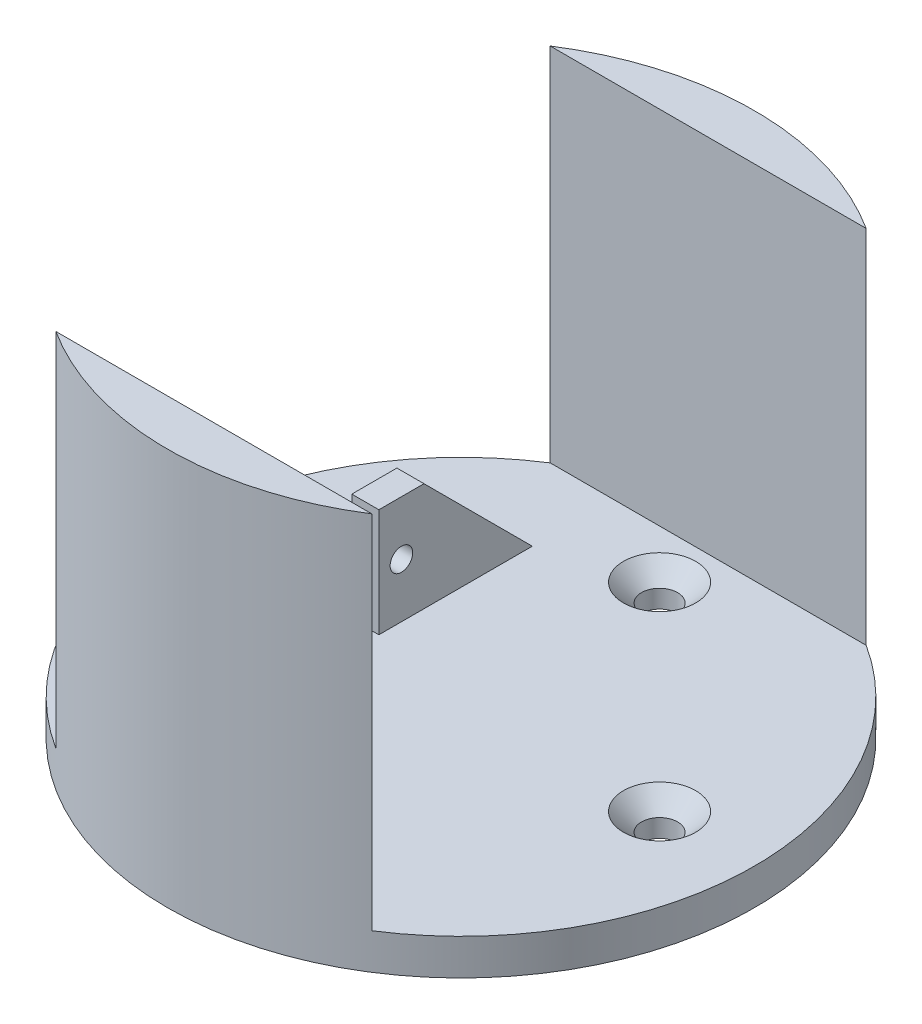
SolidWorks part; units mm, degrees
ref_plane "Front Plane" through (0, 0, 0) normal (0, 0, 1) x (1, 0, 0)
ref_plane "Top Plane" through (0, 0, 0) normal (0, 1, 0) x (1, 0, 0)
ref_plane "Right Plane" through (0, 0, 0) normal (1, 0, 0) x (0, 0, -1)
sketch "Sketch1" plane through (0, 0, 0) normal (0, 1, 0) x (1, 0, 0)
  circle A0 centre (0, 0) radius 32.5
  circle A1 centre (-22, 0) radius 2
  circle A2 centre (0, 22) radius 2
  circle A3 centre (22, 0) radius 2
  circle A4 centre (0, -22) radius 2
  point P14 (0, 0)
  dimension "D1" = 65
  dimension "D2" = 4
  dimension "D3" = 22
  dimension "D4" = 4
extrude "Boss-Extrude1" add sketch "Sketch1" along normal blind 4
sketch "Sketch2" plane through (0, 4, 0) normal (0, 1, 0) x (1, 0, 0)
  line L0 (17.5, 27.3861) -> (-17.5, 27.3861)
  line L1 (0, 0) -> (-10.9128, 0) construction
  line L2 (17.5, -27.3861) -> (-17.5, -27.3861)
  arc A0 (17.5, 27.3861) -> (-17.5, 27.3861) centre (0, 0) ccw
  arc A1 (17.5, -27.3861) -> (-17.5, -27.3861) centre (0, 0) cw
  circle A4 centre (0, 0) radius 32.5 construction
  dimension "D1" = 35
extrude "Boss-Extrude2" add sketch "Sketch2" along normal blind 40
chamfer "Chamfer1" distance 2 angle 45 4 edges at (0, 4, 24) (0, 4, -20) (22, 4, 2) (-22, 4, 2)
sketch "Sketch3" plane through (0, 4, 0) normal (0, 1, 0) x (1, 0, 0)
  line L0 (0, 0) -> (-7.2128, 0) construction
  line L1 (-13.5, 6.4) -> (-10.5, 6.4)
  line L2 (-13.5, 6.4) -> (-13.5, 1.4)
  line L3 (-13.5, 1.4) -> (-10.5, 1.4)
  line L4 (-10.5, 6.4) -> (-10.5, 1.4)
  line L5 (-13.5, 6.4) -> (-10.5, 1.4) construction
  line L6 (-13.5, 1.4) -> (-10.5, 6.4) construction
  line L8 (-10.5, -26.4) -> (-13.5, -26.4)
  line L9 (-10.5, -26.4) -> (-10.5, -21.4)
  line L10 (-10.5, -21.4) -> (-13.5, -21.4)
  line L11 (-13.5, -26.4) -> (-13.5, -21.4)
  line L12 (-10.5, -26.4) -> (-13.5, -21.4) construction
  line L13 (-10.5, -21.4) -> (-13.5, -26.4) construction
  point P0 (-12, 3.9)
  point P5 (-12, -23.9)
  point P13 (0, 0)
  dimension "D3" = 5
  dimension "D4" = 3.9
  dimension "D1" = 12
  dimension "D2" = 3
  dimension "D5" = 27.8
  dimension "D6" = 3
  dimension "D7" = 5
extrude "Boss-Extrude3" add sketch "Sketch3" along normal blind 12
sketch "Sketch4" plane through (-13.5, 0, 0) normal (-1, 0, 0) x (0, 0, 1)
  line L0 (-6.4, 4) -> (-1.4, 4) construction
  line L1 (-6.4, 16) -> (-1.4, 16) construction
  line L2 (21.4, 16) -> (26.4, 16) construction
  circle A0 centre (-3.9, 10) radius 1.25
  circle A1 centre (23.9, 10) radius 1.25
  point P6 (-3.9, 16)
  point P11 (23.9, 16)
  point P12 (0, 0)
  dimension "D1" = 2.5
  dimension "D3" = 2.5
  dimension "D2" = 6
extrude "Cut-Extrude1" cut sketch "Sketch4" against normal up to surface (3 mm away) up to face at (-10.5, 10, -3.9)
sketch "Sketch5" plane through (0, 4, 0) normal (0, 1, 0) x (1, 0, 0)
  line L0 (-28.55, 1.9) -> (-28.55, -3.1)
  line L1 (-25.55, 1.9) -> (-25.55, -3.1)
  line L2 (-28.55, 1.9) -> (-25.55, -3.1) construction
  line L3 (-28.55, -3.1) -> (-25.55, 1.9) construction
  line L4 (-13.5, 6.4) -> (-13.5, 1.4) construction
  line L5 (-13.5, 1.4) -> (-10.5, 1.4) construction
  arc A0 (-28.55, 1.9) -> (-25.55, 1.9) centre (-27.05, 1.9) cw
  arc A1 (-28.55, -3.1) -> (-25.55, -3.1) centre (-27.05, -3.1) ccw
  point P6 (-27.05, -0.6)
  dimension "D1" = 3
  dimension "D2" = 5
  dimension "D3" = 13.55
  dimension "D4" = 2
extrude "Cut-Extrude2" cut sketch "Sketch5" against normal blind 3
chamfer "Chamfer3" distance 12 angle 45 2 edges at (-12, 4, -6.4) (-12, 4, 26.4)
equation "\"D3@Sketch4\"=\"D1@Sketch4\""
equation "\"D7@Sketch3\"=\"D3@Sketch3\""
equation "\"D6@Sketch3\"=\"D2@Sketch3\""
